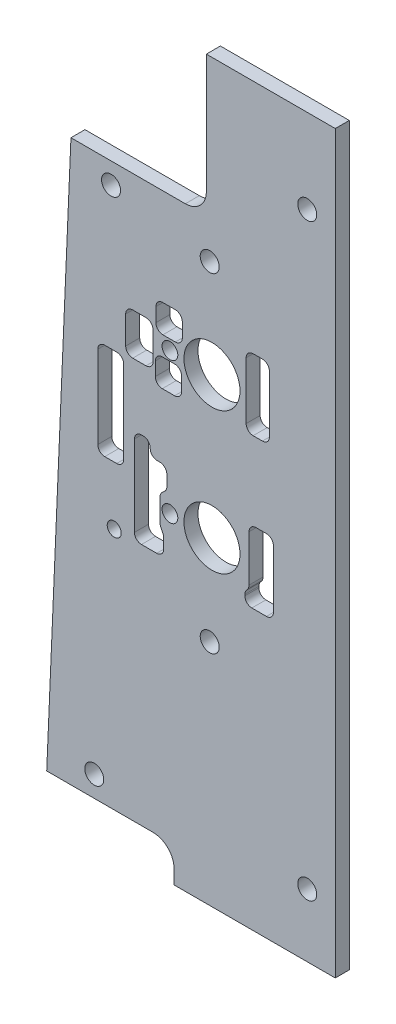
SolidWorks part; units mm, degrees
material "Acrylic (Medium-high impact)"
ref_plane "Front Plane" through (0, 0, 0) normal (0, 0, 1) x (1, 0, 0)
ref_plane "Top Plane" through (0, 0, 0) normal (0, 1, 0) x (1, 0, 0)
ref_plane "Right Plane" through (0, 0, 0) normal (1, 0, 0) x (0, 0, -1)
sketch "Sketch1" plane through (0, 0, 0) normal (0, 0, 1) x (1, 0, 0)
  line L8 (-36.5125, 0) -> (0, 0)
  line L9 (0, 0) -> (0, 166.6875)
  line L10 (0, 166.6875) -> (-29.21, 166.6875)
  line L11 (-29.21, 166.6875) -> (-29.21, 139.7)
  line L12 (-33.9725, 134.9375) -> (-59.8907, 134.9375)
  line L13 (-59.8907, 134.9375) -> (-65.3795, 7.9375)
  line L14 (-65.3795, 7.9375) -> (-41.275, 7.9375)
  line L15 (-36.5125, 3.175) -> (-36.5125, 0)
  line L16 (-36.5125, 0) -> (0, 0)
  line L17 (0, 0) -> (0, 166.6875)
  line L18 (0, 166.6875) -> (-29.21, 166.6875)
  line L19 (-29.21, 166.6875) -> (-29.21, 139.7)
  line L20 (-33.9725, 134.9375) -> (-59.8907, 134.9375)
  line L21 (-59.8907, 134.9375) -> (-65.3795, 7.9375)
  line L22 (-65.3795, 7.9375) -> (-41.275, 7.9375)
  line L23 (-36.5125, 3.175) -> (-36.5125, 0)
  arc A2 (-33.9725, 134.9375) -> (-29.21, 139.7) centre (-33.9725, 139.7) ccw
  arc A3 (-36.5125, 3.175) -> (-41.275, 7.9375) centre (-41.275, 3.175) ccw
  arc A4 (-33.9725, 134.9375) -> (-29.21, 139.7) centre (-33.9725, 139.7) ccw
  arc A5 (-36.5125, 3.175) -> (-41.275, 7.9375) centre (-41.275, 3.175) ccw
  dimension "D1" = 0
extrude "Boss-Extrude1" add sketch "Sketch1" against normal blind 3.175
hole_wizard "9/64 (0.14063) Diameter Hole1" positions "Sketch6" profile "Sketch5" hole size "9/64" standard "ANSI Inch" end condition through all
sketch "Sketch6" plane through (0, 0, 0) normal (0, 0, 1) x (1, 0, 0)
  point P0 (-18.415, 26.3525)
  point P3 (-37.465, 72.39)
  point P6 (-37.465, 104.394)
sketch "Sketch5" plane through (-18.415, 26.3525, 0) normal (1, 0, 0) x (0, -1, 0)
  line L0 (0, 0) -> (0, 3.175)
  line L1 (0, 3.175) -> (1.786, 3.175)
  line L2 (1.786, 3.175) -> (1.786, 0)
  line L5 (1.786, 0) -> (0, 0)
  line L11 (0, -6.35) -> (0, 107.95) construction
  dimension "Thru Hole Dia." = 3.572
  dimension "Thru Hole Depth" = 3.175
hole_wizard "1/2 (0.5) Diameter Hole1" positions "Sketch8" profile "Sketch7" hole size "1/2" standard "ANSI Inch" end condition through all
sketch "Sketch8" plane through (0, 0, 0) normal (0, 0, 1) x (1, 0, 0)
  point P0 (-27.94, 26.3525)
  point P3 (-27.94, 72.39)
  point P6 (-27.94, 104.394)
sketch "Sketch7" plane through (-27.94, 26.3525, 0) normal (1, 0, 0) x (0, -1, 0)
  line L0 (0, 0) -> (0, 3.175)
  line L1 (0, 3.175) -> (6.35, 3.175)
  line L2 (6.35, 3.175) -> (6.35, 0)
  line L5 (6.35, 0) -> (0, 0)
  line L11 (0, -6.35) -> (0, 107.95) construction
  dimension "Thru Hole Dia." = 12.7
  dimension "Thru Hole Depth" = 3.175
hole_wizard "#6 Clearance Hole1" positions "Sketch10" profile "Sketch9" hole size "#6" standard "ANSI Inch" end condition through all
sketch "Sketch10" plane through (0, 0, 0) normal (0, 0, 1) x (1, 0, 0)
  point P0 (-28.448, 51.7525)
  point P3 (-28.448, 126.365)
sketch "Sketch9" plane through (-28.448, 51.7525, 0) normal (1, 0, 0) x (0, -1, 0)
  line L0 (0, 0) -> (0, 3.175)
  line L1 (0, 3.175) -> (2.1526, 3.175)
  line L2 (2.1526, 3.175) -> (2.1526, 0)
  line L5 (2.1526, 0) -> (0, 0)
  line L11 (0, -6.35) -> (0, 107.95) construction
  dimension "Thru Hole Dia." = 4.3053
  dimension "Thru Hole Depth" = 3.175
hole_wizard "#6 Clearance Hole2" positions "Sketch12" profile "Sketch11" hole size "#6" standard "ANSI Inch" end condition through all
sketch "Sketch12" plane through (0, 0, 0) normal (0, 0, 1) x (1, 0, 0)
  point P0 (-50.8, 130.175)
  point P3 (-6.35, 147.6375)
  point P6 (-6.35, 14.2875)
  point P9 (-54.61, 12.7)
sketch "Sketch11" plane through (-50.8, 130.175, 0) normal (1, 0, 0) x (0, -1, 0)
  line L0 (0, 0) -> (0, 3.175)
  line L1 (0, 3.175) -> (2.1526, 3.175)
  line L2 (2.1526, 3.175) -> (2.1526, 0)
  line L5 (2.1526, 0) -> (0, 0)
  line L11 (0, -6.35) -> (0, 107.95) construction
  dimension "Thru Hole Dia." = 4.3053
  dimension "Thru Hole Depth" = 3.175
sketch "Sketch13" plane through (0, 0, 0) normal (0, 0, 1) x (1, 0, 0)
  line L1 (-36.7288, 18.4616) -> (-13.154, 18.4616)
  line L2 (-36.7288, 18.4616) -> (-36.7288, 34.3872)
  line L3 (-36.7288, 34.3872) -> (-13.154, 34.3872)
  line L4 (-13.154, 18.4616) -> (-13.154, 34.3872)
extrude "Boss-Extrude2" add sketch "Sketch13" against normal through all
sketch "Sketch14" plane through (0, 0, 0) normal (0, 0, 1) x (1, 0, 0)
  line L0 (-47.9417, 77.7812) -> (-47.9417, 96.4693)
  line L1 (-49.5292, 98.0568) -> (-52.2259, 98.0568)
  line L2 (-53.8134, 96.4693) -> (-53.8134, 77.7812)
  line L3 (-52.2259, 76.1937) -> (-49.5292, 76.1937)
  line L4 (-45.5032, 83.0253) -> (-45.5032, 64.698)
  line L5 (-43.9157, 63.1105) -> (-40.4618, 63.1105)
  line L6 (-38.8743, 64.698) -> (-38.8743, 66.9838)
  line L7 (-39.0265, 67.662) -> (-39.559, 68.7891)
  line L8 (-39.7112, 69.4674) -> (-39.7112, 74.5143)
  line L9 (-39.198, 75.6831) -> (-38.6678, 76.1704)
  line L10 (-38.1546, 77.3392) -> (-38.1546, 79.7639)
  line L11 (-39.7421, 81.3514) -> (-40.3388, 81.3514)
  line L12 (-41.9263, 82.9389) -> (-41.9263, 83.0253)
  line L13 (-43.5138, 84.6128) -> (-43.9157, 84.6128)
  line L14 (-47.4834, 100.2688) -> (-47.4834, 106.5574)
  line L15 (-45.8959, 108.1449) -> (-42.8844, 108.1449)
  line L16 (-41.2969, 106.5574) -> (-41.2969, 100.2688)
  line L17 (-42.8844, 98.6813) -> (-45.8959, 98.6813)
  line L18 (-34.656, 108.2665) -> (-34.656, 111.4221)
  line L19 (-36.2435, 113.0096) -> (-39.0579, 113.0096)
  line L20 (-40.6454, 111.4221) -> (-40.6454, 108.2665)
  line L21 (-39.0579, 106.679) -> (-36.2435, 106.679)
  line L22 (-34.8187, 97.6361) -> (-34.8187, 100.7008)
  line L23 (-36.4062, 102.2883) -> (-39.1933, 102.2883)
  line L24 (-40.7808, 100.7008) -> (-40.7808, 97.6361)
  line L25 (-39.1933, 96.0486) -> (-36.4062, 96.0486)
  line L26 (-14.918, 98.6959) -> (-14.918, 111.6098)
  line L27 (-16.5055, 113.1973) -> (-18.612, 113.1973)
  line L28 (-20.1995, 111.6098) -> (-20.1995, 98.6959)
  line L29 (-18.612, 97.1084) -> (-16.5055, 97.1084)
  line L30 (-20.4851, 64.7468) -> (-20.4851, 65.0549)
  line L31 (-20.101, 66.0903) -> (-19.919, 66.3018)
  line L33 (-17.9473, 79.3985) -> (-15.5964, 79.3985)
  line L34 (-14.0089, 77.811) -> (-14.0089, 64.7468)
  line L35 (-15.5964, 63.1593) -> (-18.8976, 63.1593)
  line L36 (-19.5348, 67.3372) -> (-19.5348, 77.811)
  arc A0 (-47.9417, 96.4693) -> (-49.5292, 98.0568) centre (-49.5292, 96.4693) ccw
  arc A1 (-52.2259, 98.0568) -> (-53.8134, 96.4693) centre (-52.2259, 96.4693) ccw
  arc A2 (-53.8134, 77.7812) -> (-52.2259, 76.1937) centre (-52.2259, 77.7812) ccw
  arc A3 (-47.9417, 77.7812) -> (-49.5292, 76.1937) centre (-49.5292, 77.7812) cw
  arc A4 (-45.5032, 83.0253) -> (-43.9157, 84.6128) centre (-43.9157, 83.0253) cw
  arc A5 (-40.3388, 81.3514) -> (-41.9263, 82.9389) centre (-40.3388, 82.9389) cw
  arc A6 (-38.1546, 79.7639) -> (-39.7421, 81.3514) centre (-39.7421, 79.7639) ccw
  arc A7 (-38.6678, 76.1704) -> (-38.1546, 77.3392) centre (-39.7421, 77.3392) ccw
  arc A8 (-39.7112, 74.5143) -> (-39.198, 75.6831) centre (-38.1237, 74.5143) cw
  arc A9 (-39.559, 68.7891) -> (-39.7112, 69.4674) centre (-38.1237, 69.4674) cw
  arc A10 (-38.8743, 66.9838) -> (-39.0265, 67.662) centre (-40.4618, 66.9838) ccw
  arc A11 (-40.4618, 63.1105) -> (-38.8743, 64.698) centre (-40.4618, 64.698) ccw
  arc A12 (-45.5032, 64.698) -> (-43.9157, 63.1105) centre (-43.9157, 64.698) ccw
  arc A13 (-41.9263, 83.0253) -> (-43.5138, 84.6128) centre (-43.5138, 83.0253) ccw
  arc A14 (-41.2969, 100.2688) -> (-42.8844, 98.6813) centre (-42.8844, 100.2688) cw
  arc A15 (-42.8844, 108.1449) -> (-41.2969, 106.5574) centre (-42.8844, 106.5574) cw
  arc A16 (-47.4834, 106.5574) -> (-45.8959, 108.1449) centre (-45.8959, 106.5574) cw
  arc A17 (-47.4834, 100.2688) -> (-45.8959, 98.6813) centre (-45.8959, 100.2688) ccw
  arc A18 (-34.656, 111.4221) -> (-36.2435, 113.0096) centre (-36.2435, 111.4221) ccw
  arc A19 (-39.0579, 113.0096) -> (-40.6454, 111.4221) centre (-39.0579, 111.4221) ccw
  arc A20 (-40.6454, 108.2665) -> (-39.0579, 106.679) centre (-39.0579, 108.2665) ccw
  arc A21 (-34.656, 108.2665) -> (-36.2435, 106.679) centre (-36.2435, 108.2665) cw
  arc A22 (-34.8187, 100.7008) -> (-36.4062, 102.2883) centre (-36.4062, 100.7008) ccw
  arc A23 (-39.1933, 102.2883) -> (-40.7808, 100.7008) centre (-39.1933, 100.7008) ccw
  arc A24 (-40.7808, 97.6361) -> (-39.1933, 96.0486) centre (-39.1933, 97.6361) ccw
  arc A25 (-34.8187, 97.6361) -> (-36.4062, 96.0486) centre (-36.4062, 97.6361) cw
  arc A26 (-14.918, 111.6098) -> (-16.5055, 113.1973) centre (-16.5055, 111.6098) ccw
  arc A27 (-18.612, 113.1973) -> (-20.1995, 111.6098) centre (-18.612, 111.6098) ccw
  arc A28 (-14.918, 98.6959) -> (-16.5055, 97.1084) centre (-16.5055, 98.6959) cw
  arc A29 (-20.1995, 98.6959) -> (-18.612, 97.1084) centre (-18.612, 98.6959) ccw
  arc A30 (-19.5348, 77.811) -> (-17.9473, 79.3985) centre (-17.9473, 77.811) cw
  arc A31 (-15.5964, 79.3985) -> (-14.0089, 77.811) centre (-15.5964, 77.811) cw
  arc A32 (-14.0089, 64.7468) -> (-15.5964, 63.1593) centre (-15.5964, 64.7468) cw
  arc A33 (-18.8976, 63.1593) -> (-20.4851, 64.7468) centre (-18.8976, 64.7468) cw
  arc A34 (-19.919, 66.3018) -> (-19.5348, 67.3372) centre (-21.1223, 67.3372) ccw
  arc A35 (-20.4851, 65.0549) -> (-20.101, 66.0903) centre (-18.8976, 65.0549) cw
  circle A36 centre (-50.0841, 63.0361) radius 1.5875
  point P108 (-50.0841, 63.0361)
  dimension "D1" = 1.5875
  dimension "D2" = 1.5875
  dimension "D3" = 1.5875
  dimension "D4" = 1.5875
  dimension "D5" = 1.5875
  dimension "D6" = 1.5875
  dimension "D7" = 1.5875
  dimension "D8" = 1.5875
extrude "Cut-Extrude1" cut sketch "Sketch14" against normal through all
